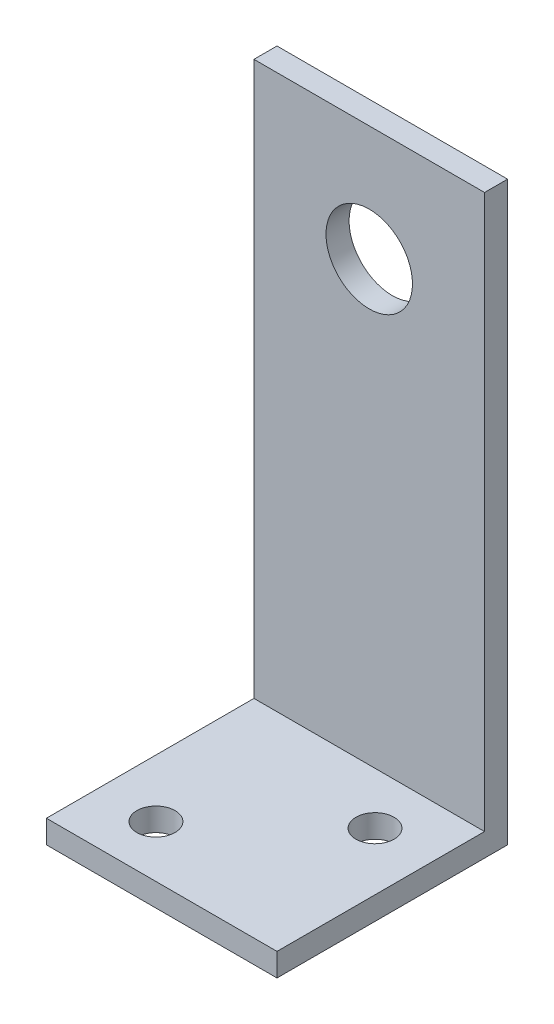
SolidWorks part; units mm, degrees
ref_plane "Front Plane" through (0, 0, 0) normal (0, 0, 1) x (1, 0, 0)
ref_plane "Top Plane" through (0, 0, 0) normal (0, 1, 0) x (1, 0, 0)
ref_plane "Right Plane" through (0, 0, 0) normal (1, 0, 0) x (0, 0, -1)
sketch "Sketch1" plane through (0, 0, 0) normal (1, 0, 0) x (0, 0, -1)
  line L0 (-25.4, 0) -> (0, 0)
  line L1 (0, 0) -> (0, 63.5)
  line L2 (-25.4, 0) -> (-25.4, 2.54)
  line L3 (-25.4, 2.54) -> (-2.54, 2.54)
  line L4 (-2.54, 2.54) -> (-2.54, 63.5)
  line L5 (-2.54, 63.5) -> (0, 63.5)
  dimension "D1" = 25.4
  dimension "D2" = 63.5
  dimension "D3" = 2.54
  dimension "D4" = 2.54
extrude "Boss-Extrude1" add sketch "Sketch1" along normal blind 12.7 and the other way blind 12.7
sketch "Sketch2" plane through (0, 0, 2.54) normal (0, 0, 1) x (1, 0, 0)
  line L0 (0, 63.5) -> (0, 0) construction
  line L1 (12.7, 63.5) -> (-12.7, 63.5) construction
  line L2 (-12.7, 0) -> (12.7, 0) construction
  circle A0 centre (0, 50.8) radius 4.7625
  dimension "D1" = 9.525
  dimension "D2" = 50.8
extrude "Cut-Extrude1" cut sketch "Sketch2" against normal blind 12.7
sketch "Sketch4" plane through (0, 2.54, 0) normal (0, 1, 0) x (1, 0, 0)
  line L0 (0, -2.54) -> (0, -25.4) construction
  line L1 (-12.7, -2.54) -> (12.7, -2.54) construction
  line L2 (-12.7, -25.4) -> (12.7, -25.4) construction
  line L3 (0, -25.4) -> (0, -13.97) construction
  line L4 (0, -13.97) -> (12.7, -13.97) construction
  line L5 (12.7, -2.54) -> (12.7, -25.4) construction
  line L6 (12.7, -13.97) -> (-12.7, -13.97) construction
  line L7 (-12.7, -2.54) -> (-12.7, -25.4) construction
  circle A0 centre (6.35, -8.255) radius 2.1
  circle A1 centre (-6.35, -19.685) radius 2.1
  point P10 (0, 0)
  dimension "D1" = 4.2
  dimension "D2" = 4.2
  dimension "D3" = 5.715
  dimension "D4" = 5.715
  dimension "D5" = 6.35
  dimension "D6" = 6.35
extrude "Cut-Extrude2" cut sketch "Sketch4" against normal through all
